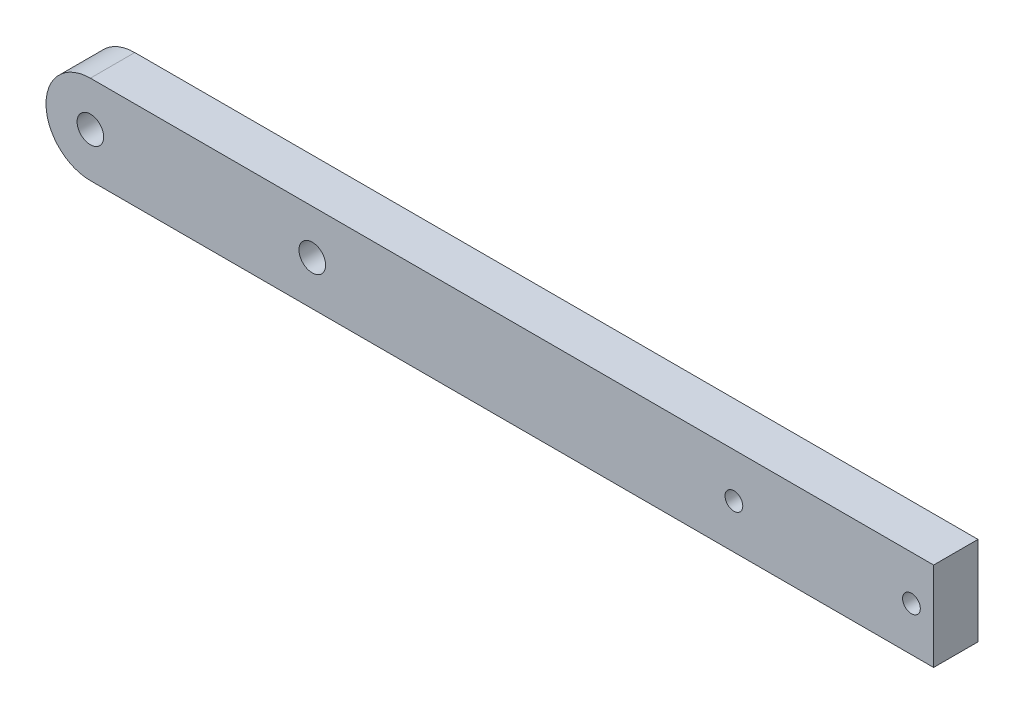
SolidWorks part; units mm, degrees
ref_plane "Front Plane" through (0, 0, 0) normal (0, 0, 1) x (1, 0, 0)
ref_plane "Top Plane" through (0, 0, 0) normal (0, 1, 0) x (1, 0, 0)
ref_plane "Right Plane" through (0, 0, 0) normal (1, 0, 0) x (0, 0, -1)
sketch "Sketch1" plane through (0, 0, 0) normal (0, 0, 1) x (1, 0, 0)
  line L1 (-100, 10) -> (100, 10)
  line L2 (-100, 10) -> (-100, -10)
  line L3 (-100, -10) -> (100, -10)
  line L4 (100, 10) -> (100, -10)
  line L5 (-100, 10) -> (100, -10) construction
  line L6 (-100, -10) -> (100, 10) construction
  circle A0 centre (-90, 0) radius 3
  circle A1 centre (-40, 0) radius 3
  circle A2 centre (95, 0) radius 2
  circle A3 centre (55, 0) radius 2
  point P0 (0, 0)
  point P14 (0, 0)
  point P15 (0, 0)
  point P16 (138.1089, 0)
  point P17 (0, 0)
  dimension "D3" = 6
  dimension "D4" = 6
  dimension "D7" = 4
  dimension "D1" = 20
  dimension "D2" = 200
  dimension "D5" = 10
  dimension "D6" = 50
  dimension "D8" = 40
  dimension "D9" = 5
extrude "Boss-Extrude1" add sketch "Sketch1" along normal blind 10
fillet "Fillet1" radius 10 2 edges at (-100, -10, 5) (-100, 10, 5)
